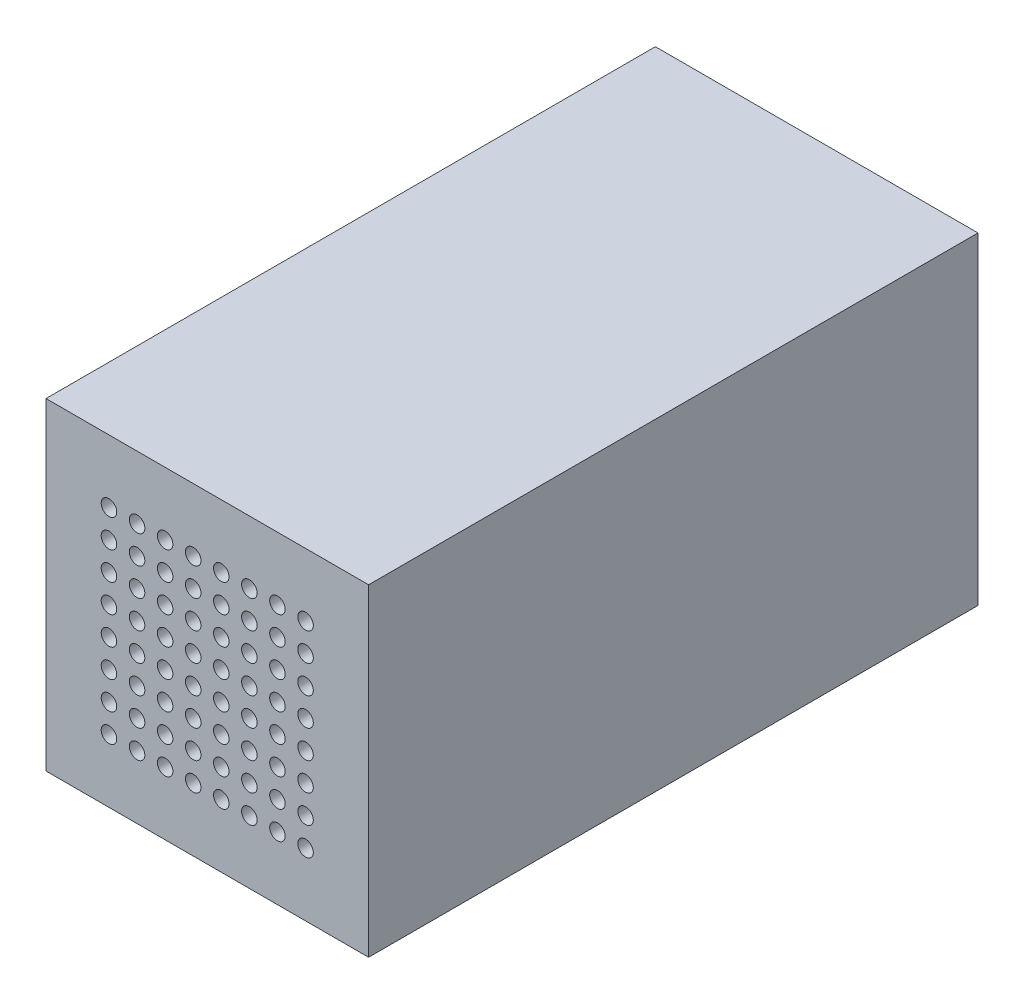
SolidWorks part; units mm, degrees
ref_plane "Front Plane" through (0, 0, 0) normal (0, 0, 1) x (1, 0, 0)
ref_plane "Top Plane" through (0, 0, 0) normal (0, 1, 0) x (1, 0, 0)
ref_plane "Right Plane" through (0, 0, 0) normal (1, 0, 0) x (0, 0, -1)
ref_plane "Plane1" through (0, 0, 43) normal (0, 0, 1) x (1, 0, 0)
sketch "Sketch2" plane through (0, 0, 43) normal (0, 0, 1) x (1, 0, 0)
  line L1 (-10, 10) -> (10, 10)
  line L2 (-10, 10) -> (-10, -10)
  line L3 (-10, -10) -> (10, -10)
  line L4 (10, 10) -> (10, -10)
  line L5 (-13.5, 13.5) -> (13.5, 13.5)
  line L6 (-13.5, 13.5) -> (-13.5, -13.5)
  line L7 (-13.5, -13.5) -> (13.5, -13.5)
  line L8 (13.5, 13.5) -> (13.5, -13.5)
  dimension "D1" = 20
  dimension "D2" = 20
  dimension "D3" = 27
  dimension "D4" = 27
  dimension "D5" = 10
  dimension "D6" = 10
  dimension "D7" = 13.5
  dimension "D8" = 13.5
sketch "Sketch5" plane through (0, 0, 43) normal (0, 0, 1) x (1, 0, 0)
  line L4 (-10, 10) -> (10, 10) construction
  line L5 (-10, 10) -> (-10, -10) construction
  line L6 (-10, -10) -> (10, -10) construction
  line L7 (10, 10) -> (10, -10) construction
  circle A0 centre (-8.23, 8.23) radius 0.65
  circle A1 centre (-5.88, 8.23) radius 0.65
  circle A2 centre (-3.53, 8.23) radius 0.65
  circle A3 centre (-1.18, 8.23) radius 0.65
  circle A4 centre (1.17, 8.23) radius 0.65
  circle A5 centre (3.52, 8.23) radius 0.65
  circle A6 centre (5.87, 8.23) radius 0.65
  circle A7 centre (8.22, 8.23) radius 0.65
  circle A8 centre (-5.88, 5.88) radius 0.65
  circle A9 centre (-3.53, 5.88) radius 0.65
  circle A10 centre (-1.18, 5.88) radius 0.65
  circle A11 centre (1.17, 5.88) radius 0.65
  circle A12 centre (3.52, 5.88) radius 0.65
  circle A13 centre (5.87, 5.88) radius 0.65
  circle A14 centre (8.22, 5.88) radius 0.65
  circle A15 centre (-5.88, 3.53) radius 0.65
  circle A16 centre (-3.53, 3.53) radius 0.65
  circle A17 centre (-1.18, 3.53) radius 0.65
  circle A18 centre (1.17, 3.53) radius 0.65
  circle A19 centre (3.52, 3.53) radius 0.65
  circle A20 centre (5.87, 3.53) radius 0.65
  circle A21 centre (8.22, 3.53) radius 0.65
  circle A22 centre (-5.88, 1.18) radius 0.65
  circle A23 centre (-3.53, 1.18) radius 0.65
  circle A24 centre (-1.18, 1.18) radius 0.65
  circle A25 centre (1.17, 1.18) radius 0.65
  circle A26 centre (3.52, 1.18) radius 0.65
  circle A27 centre (5.87, 1.18) radius 0.65
  circle A28 centre (8.22, 1.18) radius 0.65
  circle A29 centre (-5.88, -1.17) radius 0.65
  circle A30 centre (-3.53, -1.17) radius 0.65
  circle A31 centre (-1.18, -1.17) radius 0.65
  circle A32 centre (1.17, -1.17) radius 0.65
  circle A33 centre (3.52, -1.17) radius 0.65
  circle A34 centre (5.87, -1.17) radius 0.65
  circle A35 centre (8.22, -1.17) radius 0.65
  circle A36 centre (-5.88, -3.52) radius 0.65
  circle A37 centre (-3.53, -3.52) radius 0.65
  circle A38 centre (-1.18, -3.52) radius 0.65
  circle A39 centre (1.17, -3.52) radius 0.65
  circle A40 centre (3.52, -3.52) radius 0.65
  circle A41 centre (5.87, -3.52) radius 0.65
  circle A42 centre (8.22, -3.52) radius 0.65
  circle A43 centre (-5.88, -5.87) radius 0.65
  circle A44 centre (-3.53, -5.87) radius 0.65
  circle A45 centre (-1.18, -5.87) radius 0.65
  circle A46 centre (1.17, -5.87) radius 0.65
  circle A47 centre (3.52, -5.87) radius 0.65
  circle A48 centre (5.87, -5.87) radius 0.65
  circle A49 centre (8.22, -5.87) radius 0.65
  circle A50 centre (-5.88, -8.22) radius 0.65
  circle A51 centre (-3.53, -8.22) radius 0.65
  circle A52 centre (-1.18, -8.22) radius 0.65
  circle A53 centre (1.17, -8.22) radius 0.65
  circle A54 centre (3.52, -8.22) radius 0.65
  circle A55 centre (5.87, -8.22) radius 0.65
  circle A56 centre (8.22, -8.22) radius 0.65
  circle A57 centre (-8.23, 5.88) radius 0.65
  circle A58 centre (-8.23, 3.53) radius 0.65
  circle A59 centre (-8.23, 1.18) radius 0.65
  circle A60 centre (-8.23, -1.17) radius 0.65
  circle A61 centre (-8.23, -3.52) radius 0.65
  circle A62 centre (-8.23, -5.87) radius 0.65
  circle A63 centre (-8.23, -8.22) radius 0.65
  dimension "D1" = 8
  dimension "D3" = 1.3
  dimension "D4" = 2.35
  dimension "D5" = 1.77
  dimension "D6" = 1.77
  dimension "D8" = 2.35
  dimension "D2" = 8
extrude "Boss-Extrude1" add sketch "Sketch2" along normal blind 8 contours L6 L7 L8 L5
extrude "Cut-Extrude2" cut sketch "Sketch5" along normal blind 8
extrude "Boss-Extrude2" add sketch "Sketch2<6>" against normal blind 43
sketch "Sketch2<6>" plane through (0, 0, 43) normal (0, 0, 1) x (1, 0, 0) same geometry as "Sketch2"
